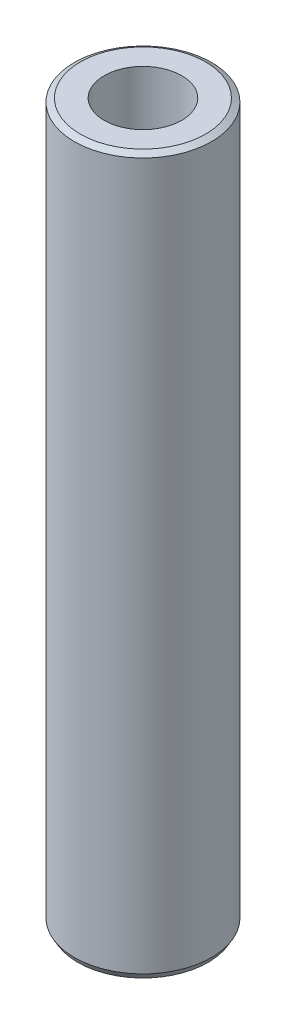
SolidWorks part; units mm, degrees
ref_plane "Front Plane" through (0, 0, 0) normal (0, 0, 1) x (1, 0, 0)
ref_plane "Top Plane" through (0, 0, 0) normal (0, 1, 0) x (1, 0, 0)
ref_plane "Right Plane" through (0, 0, 0) normal (1, 0, 0) x (0, 0, -1)
sketch "Sketch1" plane through (0, 0, 0) normal (0, 1, 0) x (1, 0, 0)
  circle A0 centre (0, 0) radius 57.5
  dimension "SHAFT_OD" = 115
extrude "Boss-Extrude1" add sketch "Sketch1" along normal blind 600
sketch "Sketch2" plane through (0, 0, 0) normal (0, 1, 0) x (1, 0, 0)
  circle A0 centre (0, 0) radius 32.4916
  dimension "BORE_D" = 64.9833
extrude "Cut-Extrude1" cut sketch "Sketch2" along normal through all
chamfer "Chamfer1" distance 2.9109 angle 60 2 edges at (0, 600, 57.5) (0, 0, 57.5) first distance on face at (0, 600, 57.5) first distance on face at (0, 0, 32.4916)
